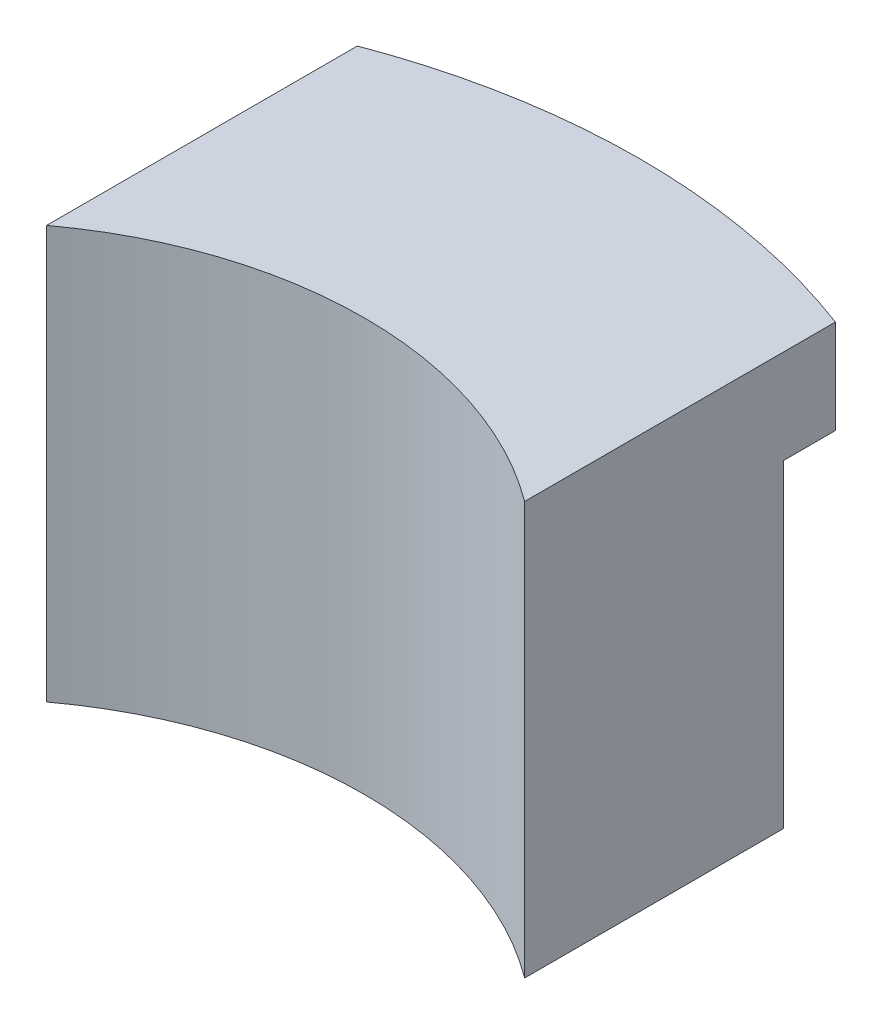
SolidWorks part; units mm, degrees
ref_plane "Front Plane" through (0, 0, 0) normal (0, 0, 1) x (1, 0, 0)
ref_plane "Top Plane" through (0, 0, 0) normal (0, 1, 0) x (1, 0, 0)
ref_plane "Right Plane" through (0, 0, 0) normal (1, 0, 0) x (0, 0, -1)
sketch "Sketch1" plane through (0, 0, 0) normal (0, 1, 0) x (1, 0, 0)
  line L1 (-15, 39.7649) -> (-15, 20.2649)
  line L2 (15, 39.7649) -> (15, 20.2649)
  arc A1 (-15, 39.7649) -> (15, 39.7649) centre (0, 0) cw
  arc A3 (-15, 20.2649) -> (15, 20.2649) centre (0, 0) cw
  dimension "D1" = 19.5
  dimension "D4" = 42.5
  dimension "D2" = 30
  dimension "D3" = 19.5
extrude "Boss-Extrude2" add sketch "Sketch1" along normal blind 2
sketch "Sketch16" plane through (0, 0, 0) normal (0, -1, 0) x (1, 0, 0)
  line L0 (15, -20.2649) -> (15, -39.7649) construction
  line L1 (-15, -20.2649) -> (-15, -39.7649)
  line L2 (15, -20.2649) -> (15, -39.7649)
  line L3 (-13, -23.9064) -> (-13, -38.3569)
  line L4 (13, -23.9064) -> (13, -38.3569)
  arc A0 (-15, -20.2649) -> (15, -20.2649) centre (0, 0) ccw
  arc A1 (-15, -39.7649) -> (15, -39.7649) centre (0, 0) ccw
  arc A4 (-13, -23.9064) -> (13, -23.9064) centre (0, 0) ccw
  arc A5 (-13, -38.3569) -> (13, -38.3569) centre (0, 0) ccw
  arc M1 (-15, -39.7649) -> (15, -39.7649) centre (0, 0) ccw
  line M2 (15, -39.7649) -> (15, -20.2649)
  arc M3 (15, -20.2649) -> (-15, -20.2649) centre (0, 0) cw
  line M4 (-15, -20.2649) -> (-15, -39.7649)
  dimension "D3" = 2
  dimension "D4" = 2
extrude "Boss-Extrude9" add sketch "Sketch16" along normal blind 3 contours A5 L3 A4 L4 M4 M1 M2 M3 region at (0, 0, -25.5859)
sketch "Sketch17" plane through (0, -3, 0) normal (0, -1, 0) x (1, 0, 0)
  line L0 (15, -39.7649) -> (15, -20.2649) construction
  line L1 (-14.5, -21.2339) -> (-14.5, -39.4176)
  line L2 (14.5, -21.2339) -> (14.5, -39.4176)
  line L3 (-15, -20.2649) -> (-15, -39.7649) construction
  arc A0 (-15, -20.2649) -> (15, -20.2649) centre (0, 0) ccw
  arc A1 (-15, -39.7649) -> (15, -39.7649) centre (0, 0) ccw
  arc A4 (-14.5, -21.2339) -> (14.5, -21.2339) centre (0, 0) ccw
  arc A5 (-14.5, -39.4176) -> (14.5, -39.4176) centre (0, 0) ccw
  line M9 (-15, -20.2649) -> (-15, -39.7649)
  arc M10 (-15, -39.7649) -> (15, -39.7649) centre (0, 0) ccw
  line M11 (15, -39.7649) -> (15, -20.2649)
  arc M12 (15, -20.2649) -> (-15, -20.2649) centre (0, 0) cw
  dimension "D1" = 0.5
  dimension "D2" = 0.5
  dimension "D3" = 0.5
  dimension "D4" = 0.5
extrude "Boss-Extrude10" add sketch "Sketch17" along normal blind 0.9 contours A5 L1 A4 L2 M12 M9 M10 M11 region at (0, -3, -25.5859)
sketch3d "3DSketch3" plane through (0, 0, 0) normal (0, 0, 1) x (1, 0, 0)
  dimension "D1" = 50
sketch "Sketch20" plane through (0, 0, -50) normal (0, 0, 1) x (1, 0, 0)
  line L0 (-15, -3.9) -> (15, -3.9) construction
  circle A0 centre (0, -3.9) radius 3.25
  dimension "D1" = 6.5
extrude "Cut-Extrude14" cut sketch "Sketch20" along normal blind 20.9
sketch "Sketch21" plane through (0, -3, 0) normal (0, -1, 0) x (1, 0, 0)
  line L0 (15, -39.7649) -> (15, -20.2649) construction
  line L1 (15, -35.6149) -> (-15, -35.6149)
  line L2 (15, -35.6149) -> (15, -18.7631)
  line L3 (15, -18.7631) -> (-15, -18.7631)
  line L4 (-15, -35.6149) -> (-15, -18.7631)
  dimension "D1" = 15.35
extrude "Cut-Extrude15" cut sketch "Sketch21" along normal blind 1
sketch "Sketch22" plane through (0, -3, 0) normal (0, -1, 0) x (1, 0, 0)
  line L0 (-15, -20.2649) -> (-15, -35.6149) construction
  line L1 (-13, -23.9064) -> (-13, -38.3569) construction
  line L2 (15, -20.2649) -> (15, -35.6149)
  line L3 (15, -35.6149) -> (13, -35.6149)
  line L4 (13, -23.9064) -> (13, -38.3569) construction
  line L5 (13, -35.6149) -> (13, -23.9064)
  line L6 (-13, -23.9064) -> (-13, -35.6149)
  line L7 (-13, -23.9064) -> (-13, -38.3569) construction
  line L8 (-13, -35.6149) -> (-15, -35.6149)
  line L9 (-15, -35.6149) -> (-15, -20.2649)
  arc A0 (15, -20.2649) -> (-15, -20.2649) centre (0, 0) cw
  arc A1 (13, -23.9064) -> (-13, -23.9064) centre (0, 0) cw
extrude "Boss-Extrude11" add sketch "Sketch22" along normal blind 20
sketch "Sketch23" plane through (0, 0, -35.6149) normal (0, 0, -1) x (-1, 0, 0)
  line L0 (-13, -23) -> (-15, -23) construction
  line L1 (-15, -3.9) -> (-14.5, -3.9)
  line L2 (-15, -3.9) -> (-15, -23)
  line L3 (-15, -23) -> (-14.5, -23)
  line L4 (-14.5, -3.9) -> (-14.5, -23)
  line L5 (15, -23) -> (13, -23) construction
  line L6 (15, -3.9) -> (14.5, -3.9)
  line L7 (15, -3.9) -> (15, -23)
  line L8 (15, -23) -> (14.5, -23)
  line L9 (14.5, -3.9) -> (14.5, -23)
  dimension "D1" = 0.5
  dimension "D2" = 0.5
extrude "Boss-Extrude12" add sketch "Sketch23" along normal blind 0.9
sketch "Sketch26" plane through (0, -23, 0) normal (0, -1, 0) x (1, 0, 0)
  line L0 (15, -36.5149) -> (15, -20.2649)
  line L1 (15, -36.5149) -> (14.5, -36.5149)
  line L2 (-15, -20.2649) -> (-15, -36.5149) construction
  line L3 (14.5, -36.5149) -> (14.5, -21.2339)
  line L4 (-15, -20.2649) -> (-15, -36.5149)
  line L5 (-15, -36.5149) -> (-14.5, -36.5149)
  line L6 (-14.5, -36.5149) -> (-14.5, -21.2339)
  arc A0 (15, -20.2649) -> (-15, -20.2649) centre (0, 0) cw
  arc A1 (14.5, -21.2339) -> (-14.5, -21.2339) centre (0, 0) cw
  dimension "D1" = 0.5
extrude "Boss-Extrude13" add sketch "Sketch26" along normal blind 0.9
